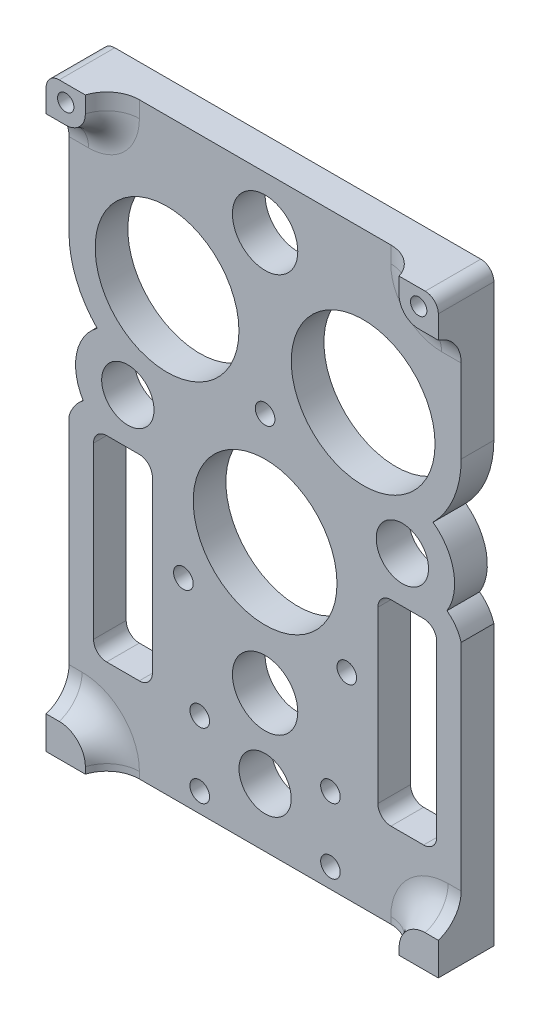
SolidWorks part; units mm, degrees
ref_plane "Front Plane" through (0, 0, 0) normal (0, 0, 1) x (1, 0, 0)
ref_plane "Top Plane" through (0, 0, 0) normal (0, 1, 0) x (1, 0, 0)
ref_plane "Right Plane" through (0, 0, 0) normal (1, 0, 0) x (0, 0, -1)
sketch "Sketch1" plane through (0, 0, 0) normal (0, 0, 1) x (1, 0, 0)
  line L1 (30, 45) -> (-30, 45)
  line L2 (30, 45) -> (30, -45)
  line L3 (30, -45) -> (-30, -45)
  line L4 (-30, 45) -> (-30, -45)
  line L5 (30, 45) -> (-30, -45) construction
  line L6 (30, -45) -> (-30, 45) construction
  point P0 (0, 0)
  dimension "D1" = 90
  dimension "D2" = 60
extrude "Boss-Extrude1" add sketch "Sketch1" along normal blind 5
sketch "Sketch2" plane through (0, 0, 0) normal (0, 0, -1) x (-1, 0, 0)
  line L0 (0, 0) -> (0, 50000) construction
  line L1 (-26.25, -2) -> (-17.25, -2)
  line L2 (-26.25, -2) -> (-26.25, -32)
  line L3 (-26.25, -32) -> (-17.25, -32)
  line L4 (-17.25, -2) -> (-17.25, -32)
  line L5 (17.25, -2) -> (26.25, -2)
  line L6 (17.25, -2) -> (17.25, -32)
  line L7 (17.25, -32) -> (26.25, -32)
  line L8 (26.25, -2) -> (26.25, -32)
  line L9 (-19.25, -30) -> (-19.25, -4) construction
  line L10 (-24.25, -4) -> (-24.25, -30) construction
  line L11 (-19.25, -4) -> (-24.25, -4) construction
  line L12 (-24.25, -30) -> (-19.25, -30) construction
  dimension "D1" = 2
  dimension "D2" = 2
  dimension "D3" = 2
  dimension "D4" = 2
extrude "Cut-Extrude1" cut sketch "Sketch2" against normal through all
fillet "Fillet1" radius 2 8 edges at (-17.25, -32, 2.5) (26.25, -32, 2.5) (17.25, -32, 2.5) (-26.25, -32, 2.5) (17.25, -2, 2.5) (26.25, -2, 2.5) (-17.25, -2, 2.5) (-26.25, -2, 2.5)
sketch "Sketch3" plane through (0, 0, 5) normal (0, 0, 1) x (1, 0, 0)
  line L0 (28, -40) -> (30, -40)
  line L1 (30, -45) -> (30, 45) construction
  line L2 (30, -40) -> (30, -45)
  line L3 (30, -45) -> (24, -45)
  line L4 (-30, -45) -> (30, -45) construction
  line L5 (24, -45) -> (24, -44)
  line L6 (24, -47.5) -> (24, -45) construction
  arc A0 (24, -44) -> (28, -40) centre (28, -44) cw
  dimension "D1" = 4
  dimension "D2" = 5
extrude "Boss-Extrude2" add sketch "Sketch3" along normal up to surface (3.5 mm away) up to face at (-21.75, -17, 0)
fillet "Fillet2" radius 5 3 edges at (25.1716, -41.1716, 5)
mirror "Mirror1" about plane through (0, 0, 0) normal (1, 0, 0) of "Fillet2", "Boss-Extrude2"
sketch "Sketch4" plane through (0, 0, 5) normal (0, 0, 1) x (1, 0, 0)
  line L0 (24, 45) -> (24, 42.5)
  line L1 (30, 45) -> (-30, 45) construction
  line L2 (24, 45) -> (30, 45)
  line L3 (30, 45) -> (30, 39.5)
  line L4 (30, -35.2303) -> (30, 45) construction
  line L5 (30, 39.5) -> (27, 39.5)
  arc A0 (27, 39.5) -> (24, 42.5) centre (27, 42.5) cw
  dimension "D1" = 3
extrude "Boss-Extrude3" add sketch "Sketch4" along normal up to surface (3.5 mm away) up to face at (-21.75, -17, 0)
sketch "Sketch5" plane through (0, 0, 8.5) normal (0, 0, 1) x (1, 0, 0)
  circle A0 centre (27, 42.5) radius 1.25
  dimension "D1" = 2.5
extrude "Cut-Extrude2" cut sketch "Sketch5" against normal through all
fillet "Fillet3" radius 5 3 edges at (24, 43.75, 5) (24.8787, 40.3787, 5) (28.5, 39.5, 5)
mirror "Mirror4" about plane through (0, 0, 0) normal (1, 0, 0) of "Fillet3", "Boss-Extrude3", "Cut-Extrude2"
fillet "Fillet4" radius 2 2 edges at (30, 45, 4.25) (-30, 45, 4.25)
sketch "Sketch6" plane through (0, 0, 0) normal (0, 0, -1) x (-1, 0, 0)
  circle A0 centre (-10, -32) radius 1.5
  circle A1 centre (-10, -42) radius 1.5
  circle A2 centre (10, -42) radius 1.5
  circle A3 centre (10, -32) radius 1.5
  circle A4 centre (0, 13) radius 1.5
  circle A5 centre (12.5, -15) radius 1.5
  circle A6 centre (-12.5, -15) radius 1.5
  dimension "D1" = 3
extrude "Cut-Extrude3" cut sketch "Sketch6" against normal through all
sketch "Sketch7" plane through (0, 0, 5) normal (0, 0, 1) x (1, 0, 0)
  line L0 (0, 0) -> (0, 50000) construction
  line L1 (-9.5906, 22) -> (49990.4094, 22) construction
  line L2 (19.2303, 45) -> (-19.2303, 45) construction
  line L3 (-12.3292, 5) -> (49987.6708, 5) construction
  line L4 (30, 22) -> (30, 5)
  line L5 (30, -35.2303) -> (30, 34.7303) construction
  line L6 (30, 5) -> (30, -2.2861)
  line L7 (-30, 5) -> (-30, -2.2861)
  line L8 (-30, 22) -> (-30, 5)
  circle A0 centre (-15, 22) radius 11
  circle A1 centre (15, 22) radius 11
  circle A2 centre (0, -4) radius 11
  circle A3 centre (0, -24) radius 5
  circle A4 centre (0, -36) radius 4
  circle A5 centre (0, 37) radius 5
  circle A6 centre (-21, 5) radius 4
  circle A7 centre (21, 5) radius 4
  arc A8 (30, -2.2861) -> (27.8218, 0.8211) centre (24.25, -4) ccw
  arc A9 (25.6921, 11.4796) -> (27.8218, 0.8211) centre (21, 5) cw
  arc A10 (-30, -2.2861) -> (-27.8218, 0.8211) centre (-24.25, -4) cw
  arc A11 (25.6921, 11.4796) -> (30, 22) centre (15, 22) ccw
  arc A12 (26.25, -4) -> (24.25, -2) centre (24.25, -4) ccw construction
  arc A13 (-25.6921, 11.4796) -> (-27.8218, 0.8211) centre (-21, 5) ccw
  arc A14 (-25.6921, 11.4796) -> (-30, 22) centre (-15, 22) cw
  dimension "D2" = 22
  dimension "D4" = 26
  dimension "D5" = 10
  dimension "D6" = 8
  dimension "D10" = 10
  dimension "D11" = 8
  dimension "D14" = 6
  dimension "D15" = 8
  dimension "D1" = 30
  dimension "D3" = 23
  dimension "D7" = 20
  dimension "D8" = 12
  dimension "D9" = 8
  dimension "D12" = 42
  dimension "D13" = 17
extrude "Cut-Extrude4" cut sketch "Sketch7" against normal through all
